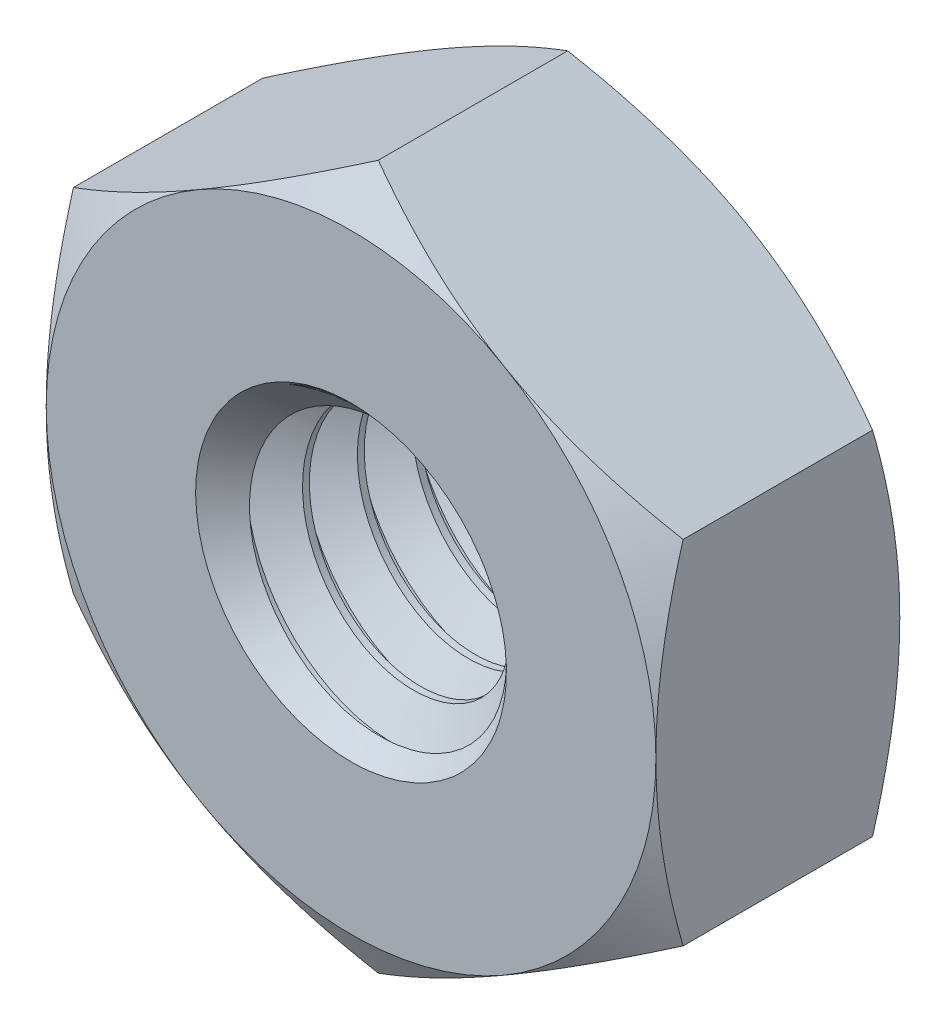
SolidWorks part; units mm, degrees
ref_plane "Front Plane" through (0, 0, 0) normal (0, 0, 1) x (1, 0, 0)
ref_plane "Top Plane" through (0, 0, 0) normal (0, 1, 0) x (1, 0, 0)
ref_plane "Right Plane" through (0, 0, 0) normal (1, 0, 0) x (0, 0, -1)
sketch "Sketch1" plane through (0, 0, 0) normal (1, 0, 0) x (0, 0, -1)
  line L0 (-1, 0) -> (1, 0) construction
  line L1 (-1, -2.5) -> (-1, 2.5) construction
  line L2 (1, -2.5) -> (1, 2.5) construction
  line L3 (-1, -1.25) -> (-1, 1.25) construction
  line L4 (-1.4219, 1.2987) -> (-1.1969, 0.909) construction
  line L5 (-1.1969, 0.909) -> (-0.9719, 1.2987) construction
  line L6 (-0.9719, 1.2987) -> (-1.4219, 1.2987) construction
  line L7 (-1.4078, 1.2744) -> (-0.9859, 1.2744) construction
  line L8 (-1.3938, 1.25) -> (-1, 1.25) construction
  line L9 (-1.225, 0.9577) -> (-1.1688, 0.9577) construction
  line L10 (-1.1969, 0.9577) -> (-1.1969, 0.909) construction
  line L11 (-1.1969, 1.2987) -> (-1.1969, 1.25) construction
  point P4 (0, 0)
  point P7 (-1, 0)
  point P11 (1, 0)
  point P14 (-1, 0)
  point P26 (-1.1969, 1.2744)
  point P27 (-1, -1.25)
  dimension "Height" = 2
  dimension "Width" = 5
  dimension "Thread OD" = 2.5
  dimension "D1" = 60
  dimension "Pitch" = 0.45
  dimension "D2" = 0.0563
sketch "Sketch2" plane through (0, 0, 0) normal (0, 0, 1) x (1, 0, 0)
  line L1 (0, 2.8868) -> (-2.5, 1.4434)
  line L2 (-2.5, 1.4434) -> (-2.5, -1.4434)
  line L3 (-2.5, -1.4434) -> (0, -2.8868)
  line L4 (0, -2.8868) -> (2.5, -1.4434)
  line L5 (2.5, -1.4434) -> (2.5, 1.4434)
  line L6 (2.5, 1.4434) -> (0, 2.8868)
  circle A0 centre (0, 0) radius 2.5 construction
  circle A1 centre (0, 0) radius 1.25
extrude "Boss-Extrude1" add sketch "Sketch2" along normal up to vertex (1 mm away) and the other way up to vertex (1 mm away) up to point (0, -2.5, 1) other way up to point (0, -2.5, -1)
sketch "Sketch3" plane through (0, 0, 1) normal (0, 0, 1) x (1, 0, 0)
  circle A0 centre (0, 0) radius 2.5
extrude "Cut-Extrude1" cut sketch "Sketch3" against normal through all draft 60 flip side to cut
mirror "Mirror1" about plane through (0, 0, 0) normal (0, 0, 1) of "Cut-Extrude1"
ref_axis "Center Axis 1" through (0, 0, -10.9016) along (0, 0, 1)
ref_plane "Contact Plane 1" through (0, 0, 1) normal (0, 0, 1) x (1, 0, 0)
ref_plane "Contact Plane 2" through (0, 0, -1) normal (0, 0, -1) x (-1, 0, 0)
sketch "Sketch4" plane through (0, 0, 0) normal (1, 0, 0) x (0, 0, -1)
  line L1 (-1.4078, 1.2744) -> (-1.225, 0.9577)
  line L2 (-1.225, 0.9577) -> (-1.1688, 0.9577)
  line L3 (-1.1688, 0.9577) -> (-0.9859, 1.2744)
  line L4 (-1.4078, 1.2744) -> (-0.9859, 1.2744) construction
  line L5 (-1.4078, 1.2744) -> (-0.9859, 1.2744)
sketch "Sketch5" plane through (0, 0, 1) normal (0, 0, 1) x (1, 0, 0)
  circle A0 centre (0, 0) radius 1.25 construction
  circle A1 centre (0, 0) radius 1.25
curve "Helix/Spiral1" pitch 0.45 height 2.45 radius 1.25 centre (0, 0, 1) axis (0, 0, -1) start towards (0, 1, 0)
sweep "Sweep1" add profiles "Sketch4" path "Helix/Spiral1"
sketch "Sketch6" plane through (0, 0, 1) normal (0, 0, 1) x (1, 0, 0)
  circle A1 centre (0, 0) radius 1.2744
extrude "Cut-Extrude2" cut sketch "Sketch6" along normal through all and the other way through all draft 45
sketch "Sketch7" plane through (0, 0, -1) normal (0, 0, -1) x (-1, 0, 0)
  circle A1 centre (0, 0) radius 1.2744
  circle A2 centre (0, 0) radius 1.2744
  dimension "D1" = 0
extrude "Cut-Extrude3" cut sketch "Sketch7" along normal through all and the other way through all draft 45
equation "\"D2@Sketch1\"=\"Pitch@Sketch1\"/8"
equation "\"D4@Helix/Spiral1\"=\"Pitch@Sketch1\""
equation "\"D3@Helix/Spiral1\"=\"Height@Sketch1\"+\"Pitch@Sketch1\""
